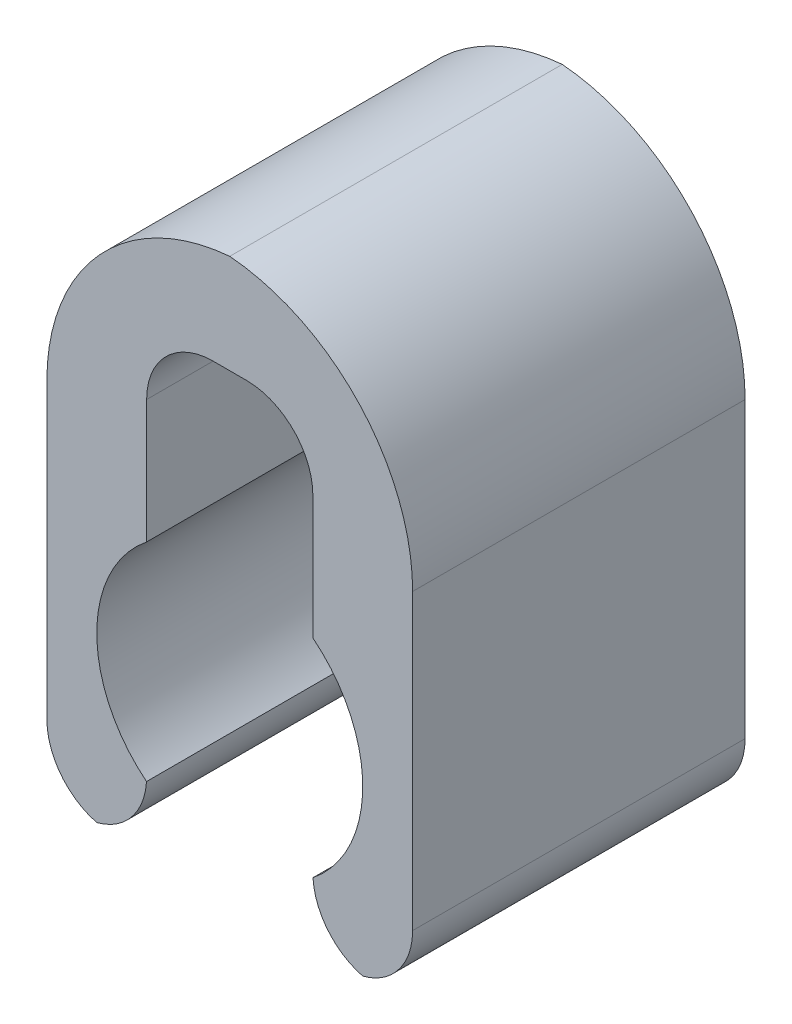
SolidWorks part; units mm, degrees
ref_plane "Front Plane" through (0, 0, 0) normal (0, 0, 1) x (1, 0, 0)
ref_plane "Top Plane" through (0, 0, 0) normal (0, 1, 0) x (1, 0, 0)
ref_plane "Right Plane" through (0, 0, 0) normal (1, 0, 0) x (0, 0, -1)
sketch "Sketch1" plane through (0, 0, 0) normal (0, 0, 1) x (1, 0, 0)
  line L0 (-27.1712, -6.1809) -> (-27.1712, -9.3479)
  line L1 (-27.1712, -2.5149) -> (-22.1712, -2.5149)
  line L2 (-27.1712, -2.5149) -> (-27.1712, 4.4851)
  line L3 (-27.1712, 4.4851) -> (-22.1712, 4.4851)
  line L4 (-22.1712, -2.5149) -> (-22.1712, 4.4851)
  line L5 (-30.1712, 7.4851) -> (-19.1712, 7.4851)
  line L6 (-30.1712, 7.4851) -> (-30.1712, -9.3479)
  line L7 (-30.1712, -9.3479) -> (-19.1712, -9.3479)
  line L8 (-19.1712, 7.4851) -> (-19.1712, -9.3479)
  line L9 (-22.1712, -6.1809) -> (-22.1712, -9.3479)
  circle A0 centre (-24.6712, -4.3479) radius 3.1
  dimension "D1" = 6.2
  dimension "D2" = 5
  dimension "D3" = 7
  dimension "D4" = 3
  dimension "D5" = 3
  dimension "D6" = 3
  dimension "D7" = 5
  dimension "D8" = 5.5
extrude "Boss-Extrude1" add sketch "Sketch1" along normal blind 10 contours A0 L9 L7 L8 L5 L6 L0 L2 L3 L4 region at (-27.3723, -7.7644, 0)
fillet "Fillet1" radius 6 2 edges at (-19.1712, 7.4851, 5) (-30.1712, 7.4851, 5)
fillet "Fillet2" radius 2 4 edges at (-19.1712, -9.3479, 5) (-22.1712, -9.3479, 5) (-27.1712, -9.3479, 5) (-30.1712, -9.3479, 5)
fillet "Fillet3" radius 2 2 edges at (-27.1712, 4.4851, 5) (-22.1712, 4.4851, 5)
sketch "Sketch2" plane through (0, 0, 10) normal (0, 0, 1) x (1, 0, 0)
  circle A0 centre (-24.6712, -4.3479) radius 4
  dimension "D1" = 8
extrude "Cut-Extrude1" cut sketch "Sketch2" against normal through all
